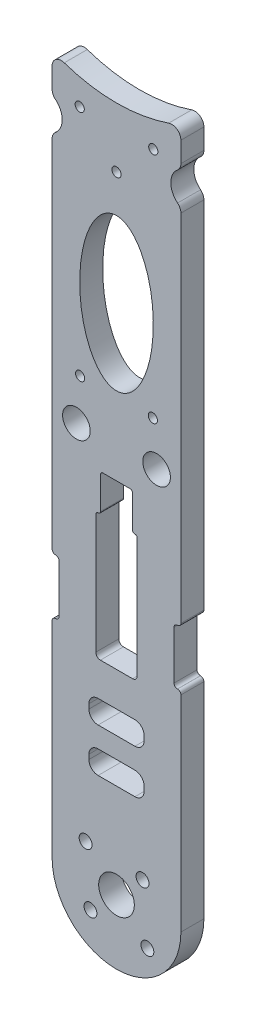
SolidWorks part; units mm, degrees
ref_plane "Front Plane" through (0, 0, 0) normal (0, 0, 1) x (1, 0, 0)
ref_plane "Top Plane" through (0, 0, 0) normal (0, 1, 0) x (1, 0, 0)
ref_plane "Right Plane" through (0, 0, 0) normal (1, 0, 0) x (0, 0, -1)
sketch "Sketch1" plane through (0, 0, 0) normal (0, 0, 1) x (1, 0, 0)
  line L0 (-14, 0) -> (-14, 44.6414)
  line L1 (0, 149.0732) -> (0, -14) construction
  line L2 (14, 0) -> (14, 44.6414)
  line L3 (-14, 0) -> (14, 0) construction
  line L4 (-6.7175, 6.7175) -> (6.7175, -6.7175) construction
  line L5 (-4, 29.9839) -> (4, 29.9839)
  line L6 (-9.9779, -9.9779) -> (8.2462, 8.2462) construction
  line L7 (-14, 144.6611) -> (-14, 149.0732)
  line L8 (-4, 20.4839) -> (4, 20.4839)
  line L9 (-6, 22.4839) -> (-6, 23.4839)
  line L10 (-4, 25.4839) -> (4, 25.4839)
  line L11 (6, 22.4839) -> (6, 23.4839)
  line L12 (-6, 20.4839) -> (6, 25.4839) construction
  line L13 (-6, 25.4839) -> (6, 20.4839) construction
  line L14 (14, 144.6611) -> (14, 149.0732)
  line L15 (-6, 31.9839) -> (-6, 32.9839)
  line L16 (-4, 34.9839) -> (4, 34.9839)
  line L17 (6, 31.9839) -> (6, 32.9839)
  line L18 (-6, 29.9839) -> (6, 34.9839) construction
  line L19 (-6, 34.9839) -> (6, 29.9839) construction
  line L20 (-27.4948, 56.4445) -> (23.2365, 56.4445) construction
  line L21 (-3.501, 42.4445) -> (3.501, 42.4445)
  line L22 (-4.501, 43.4445) -> (-4.501, 69.4445)
  line L23 (-3.9661, 70.4274) -> (-3.4664, 70.4439) construction
  line L24 (4.501, 43.4445) -> (4.501, 69.4445)
  line L25 (-4.501, 42.4445) -> (4.5011, 77.4439) construction
  line L26 (-3.4664, 70.4439) -> (-3.4664, 77.4439)
  line L27 (-4, 51.3814) -> (0, 51.3814) construction
  line L28 (-13.26, 57.3814) -> (-13.24, 57.3814)
  line L29 (-12.5, 56.6414) -> (-12.5, 46.1214)
  line L30 (-13.26, 45.3814) -> (-13.24, 45.3814)
  line L31 (13.26, 45.3814) -> (13.24, 45.3814)
  line L32 (12.5, 56.6414) -> (12.5, 46.1214)
  line L33 (13.26, 57.3814) -> (13.24, 57.3814)
  line L34 (14, 58.1214) -> (14, 135.3474)
  line L35 (-14, 58.1214) -> (-14, 135.3474)
  line L36 (-2.9653, 77.9417) -> (2.9653, 77.9417)
  line L37 (4.5011, 77.4439) -> (-4.2262, 77.4439) construction
  line L38 (0, 59.9439) -> (4.501, 42.4445) construction
  line L39 (3.4664, 70.4439) -> (3.4664, 77.4439)
  arc A0 (-14, 0) -> (14, 0) centre (0, 0) ccw
  arc A1 (-11.3514, 150.9651) -> (11.3514, 150.9651) centre (0, 184.0732) ccw
  circle A2 centre (-8, 144.3712) radius 1
  circle A3 centre (6.7175, -6.7175) radius 1.4
  circle A4 centre (-5.6569, -5.6569) radius 1.4
  circle A5 centre (5.6569, 5.6569) radius 1.4
  circle A6 centre (-6.7175, 6.7175) radius 1.4
  circle A7 centre (8, 144.3712) radius 1
  circle A8 centre (0, 136.0732) radius 1
  circle A9 centre (0, 136.0732) radius 1 construction
  circle A10 centre (-8, 144.3712) radius 1 construction
  circle A11 centre (8, 144.3712) radius 1 construction
  circle A12 centre (-7.9033, 93.7383) radius 1
  circle A13 centre (0, 184.0732) radius 35 construction
  arc A14 (6, 31.9839) -> (4, 29.9839) centre (4, 31.9839) cw
  arc A15 (4, 34.9839) -> (6, 32.9839) centre (4, 32.9839) cw
  circle A16 centre (-7.9033, 93.7383) radius 1 construction
  arc A17 (-4, 34.9839) -> (-6, 32.9839) centre (-4, 32.9839) ccw
  arc A18 (-6, 31.9839) -> (-4, 29.9839) centre (-4, 31.9839) ccw
  arc A19 (4.501, 43.4445) -> (3.501, 42.4445) centre (3.501, 43.4445) cw
  circle A20 centre (-8.7156, 84.4537) radius 3
  circle A21 centre (-8.7156, 84.4537) radius 1.45 construction
  arc A22 (6, 22.4839) -> (4, 20.4839) centre (4, 22.4839) cw
  arc A23 (4, 25.4839) -> (6, 23.4839) centre (4, 23.4839) cw
  arc A24 (-4, 25.4839) -> (-6, 23.4839) centre (-4, 23.4839) ccw
  arc A25 (-6, 22.4839) -> (-4, 20.4839) centre (-4, 22.4839) ccw
  arc A26 (-14, 149.0732) -> (-11.3514, 150.9651) centre (-12, 149.0732) cw
  arc A27 (11.3514, 150.9651) -> (14, 149.0732) centre (12, 149.0732) cw
  arc A28 (-13.2731, 143.1186) -> (-13.2731, 136.8899) centre (-15.8435, 140.0042) cw
  arc A29 (13.2731, 143.1186) -> (13.2731, 136.8899) centre (15.8435, 140.0042) ccw
  arc A30 (14, 135.3474) -> (13.2731, 136.8899) centre (12, 135.3474) ccw
  arc A31 (13.2731, 143.1186) -> (14, 144.6611) centre (12, 144.6611) ccw
  arc A32 (-14, 144.6611) -> (-13.2731, 143.1186) centre (-12, 144.6611) ccw
  arc A33 (-13.2731, 136.8899) -> (-14, 135.3474) centre (-12, 135.3474) ccw
  circle A34 centre (7.9033, 93.7383) radius 1
  circle A35 centre (8.7156, 84.4537) radius 3
  arc A36 (-3.501, 42.4445) -> (-4.501, 43.4445) centre (-3.501, 43.4445) cw
  arc A37 (-4.501, 69.4445) -> (-3.9837, 69.9277) centre (-4.0013, 69.428) cw
  arc A38 (-3.9837, 69.9277) -> (-3.4664, 70.4439) centre (-3.9661, 70.4274) ccw
  arc A39 (-14, 44.6414) -> (-13.26, 45.3814) centre (-13.26, 44.6414) cw
  arc A40 (-13.24, 45.3814) -> (-12.5, 46.1214) centre (-13.24, 46.1214) ccw
  arc A41 (-12.5, 56.6414) -> (-13.24, 57.3814) centre (-13.24, 56.6414) ccw
  arc A42 (-13.26, 57.3814) -> (-14, 58.1214) centre (-13.26, 58.1214) cw
  arc A43 (12.5, 46.1214) -> (13.24, 45.3814) centre (13.24, 46.1214) ccw
  arc A44 (13.26, 45.3814) -> (14, 44.6414) centre (13.26, 44.6414) cw
  arc A45 (13.24, 57.3814) -> (12.5, 56.6414) centre (13.24, 56.6414) ccw
  arc A46 (13.26, 57.3814) -> (14, 58.1214) centre (13.26, 58.1214) ccw
  arc A47 (-3.4664, 77.4439) -> (-2.9653, 77.9417) centre (-2.9664, 77.4417) cw
  arc A48 (3.4664, 77.4439) -> (2.9653, 77.9417) centre (2.9664, 77.4417) ccw
  arc A49 (4.501, 69.4445) -> (3.9837, 69.9277) centre (4.0013, 69.428) ccw
  arc A50 (3.9837, 69.9277) -> (3.4664, 70.4439) centre (3.9661, 70.4274) cw
  ellipse E1 centre (0, 111.3839) end of major axis (0, 127.8839) minor radius 8
  point P33 (0, 32.4839)
  point P43 (0, 22.9839)
  point P82 (-14, 151.9952)
  point P85 (14, 151.9952)
  point P94 (14, 136.4115)
  point P97 (14, 143.597)
  point P100 (-14, 143.597)
  point P103 (-14, 136.4115)
  point P109 (0, 59.9439)
  point P135 (-12.5, 51.3814)
  point P141 (-14, 45.3814)
  point P144 (-12.5, 45.3814)
  point P147 (-12.5, 57.3814)
  point P150 (-14, 57.3814)
  point P153 (12.5, 45.3814)
  point P156 (14, 45.3814)
  point P159 (12.5, 57.3814)
  point P162 (14, 57.3814)
  point P171 (0, 77.9417)
  dimension "D3" = 14
  dimension "D5" = 2
  dimension "D2" = 2
  dimension "D4" = 12
  dimension "D8" = 35
  dimension "D10" = 0.5
  dimension "D11" = 9.5
  dimension "D7" = 2
  dimension "D15" = 2
  dimension "D16" = 2
  dimension "D18" = 2.8
  dimension "D19" = 9.5
  dimension "D20" = 8
  dimension "D14" = 1
  dimension "D24" = 0.74
  dimension "D12" = 0.5
  dimension "D26" = 7
  dimension "D6" = 5
  dimension "D9" = 4.5
  dimension "D13" = 8
  dimension "D17" = 8
  dimension "D21" = 1.5
  dimension "D22" = 163.0732
  dimension "D23" = 6
  dimension "D25" = 14
extrude "Boss-Extrude1" add sketch "Sketch1" along normal blind 5
sketch "Sketch2" plane through (0, 0, 5) normal (0, 0, 1) x (1, 0, 0)
  circle A0 centre (0, 0) radius 3.875
extrude "Cut-Extrude1" cut sketch "Sketch2" against normal up to next
